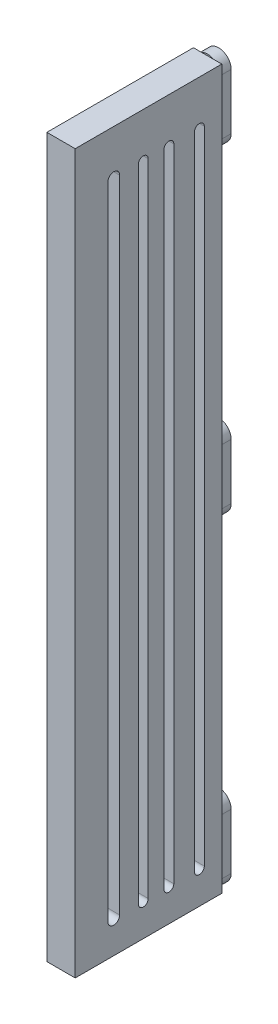
SolidWorks part; units mm, degrees
ref_plane "Front Plane" through (0, 0, 0) normal (0, 0, 1) x (1, 0, 0)
ref_plane "Top Plane" through (0, 0, 0) normal (0, 1, 0) x (1, 0, 0)
ref_plane "Right Plane" through (0, 0, 0) normal (1, 0, 0) x (0, 0, -1)
sketch "Sketch1" plane through (0, 0, 0) normal (0, 0, 1) x (1, 0, 0)
  line L1 (1.9338, -49) -> (-1.9338, -49)
  line L2 (1.9338, -49) -> (1.9338, 49)
  line L3 (1.9338, 49) -> (-1.9338, 49)
  line L4 (-1.9338, -49) -> (-1.9338, 49)
  line L5 (1.9338, -49) -> (-1.9338, 49) construction
  line L6 (1.9338, 49) -> (-1.9338, -49) construction
  line L9 (0, 3.795) -> (0, -3.795) construction
  line L10 (1.71, 3.795) -> (1.71, -3.795)
  line L11 (-1.71, 3.795) -> (-1.71, -3.795)
  line L18 (0, -39.915) -> (0, -47.505) construction
  line L19 (1.71, -39.915) -> (1.71, -47.505)
  line L20 (-1.71, -39.915) -> (-1.71, -47.505)
  line L29 (0, 47.505) -> (0, 39.915) construction
  line L30 (1.71, 47.505) -> (1.71, 39.915)
  line L31 (-1.71, 47.505) -> (-1.71, 39.915)
  arc A2 (1.71, 3.795) -> (-1.71, 3.795) centre (0, 3.795) ccw
  arc A3 (-1.71, -3.795) -> (1.71, -3.795) centre (0, -3.795) ccw
  arc A8 (1.71, -39.915) -> (-1.71, -39.915) centre (0, -39.915) ccw
  arc A9 (-1.71, -47.505) -> (1.71, -47.505) centre (0, -47.505) ccw
  arc A16 (1.71, 47.505) -> (-1.71, 47.505) centre (0, 47.505) ccw
  arc A17 (-1.71, 39.915) -> (1.71, 39.915) centre (0, 39.915) ccw
  point P0 (0, 0)
  point P5 (0, 0)
  point P6 (0, 0)
  point P13 (0, 0)
  point P34 (0, -43.71)
  point P56 (0, 43.71)
  point P71 (0, 0)
  dimension "D1" = 3.8676
  dimension "D2" = 98
extrude "Boss-Extrude3" add sketch "Sketch1" along normal blind 20 contours L4 L3 L2 L1
extrude "Boss-Extrude4" add sketch "Sketch1<6>" against normal blind 1.5 contours A17 L30 A16 L31 | A3 L10 A2 L11 | A8 L20 A9 L19
sketch "Sketch1<6>" plane through (0, 0, 0) normal (0, 0, 1) x (1, 0, 0) same geometry as "Sketch1"
sketch "Sketch5" plane through (1.9338, 0, 0) normal (1, 0, 0) x (0, 0, -1)
  line L0 (-14.7404, 42.8385) -> (-14.7404, -44.5843) construction
  line L1 (-13.9347, 42.8385) -> (-13.9347, -44.5843)
  line L2 (-15.5462, 42.8385) -> (-15.5462, -44.5843)
  line L3 (-10.7117, 42.8385) -> (-10.7117, -44.5843) construction
  line L4 (-10.0403, 42.8385) -> (-10.0403, -44.5843)
  line L5 (-11.3832, 42.8385) -> (-11.3832, -44.5843)
  line L6 (-7.2202, 42.8385) -> (-7.2202, -44.5843) construction
  line L7 (-6.5487, 42.8385) -> (-6.5487, -44.5843)
  line L8 (-7.8916, 42.8385) -> (-7.8916, -44.5843)
  line L9 (-3.0572, 42.8385) -> (-3.0572, -44.5843) construction
  line L10 (-2.3858, 42.8385) -> (-2.3858, -44.5843)
  line L11 (-3.7287, 42.8385) -> (-3.7287, -44.5843)
  arc A0 (-13.9347, 42.8385) -> (-15.5462, 42.8385) centre (-14.7404, 42.8385) ccw
  arc A1 (-15.5462, -44.5843) -> (-13.9347, -44.5843) centre (-14.7404, -44.5843) ccw
  arc A2 (-10.0403, 42.8385) -> (-11.3832, 42.8385) centre (-10.7117, 42.8385) ccw
  arc A3 (-11.3832, -44.5843) -> (-10.0403, -44.5843) centre (-10.7117, -44.5843) ccw
  arc A4 (-6.5487, 42.8385) -> (-7.8916, 42.8385) centre (-7.2202, 42.8385) ccw
  arc A5 (-7.8916, -44.5843) -> (-6.5487, -44.5843) centre (-7.2202, -44.5843) ccw
  arc A6 (-2.3858, 42.8385) -> (-3.7287, 42.8385) centre (-3.0572, 42.8385) ccw
  arc A7 (-3.7287, -44.5843) -> (-2.3858, -44.5843) centre (-3.0572, -44.5843) ccw
  point P2 (-14.7404, -0.8729)
  point P7 (-10.7117, -0.8729)
  point P14 (-7.2202, -0.8729)
  point P21 (-3.0572, -0.8729)
extrude "Cut-Extrude1" cut sketch "Sketch5" against normal through all
